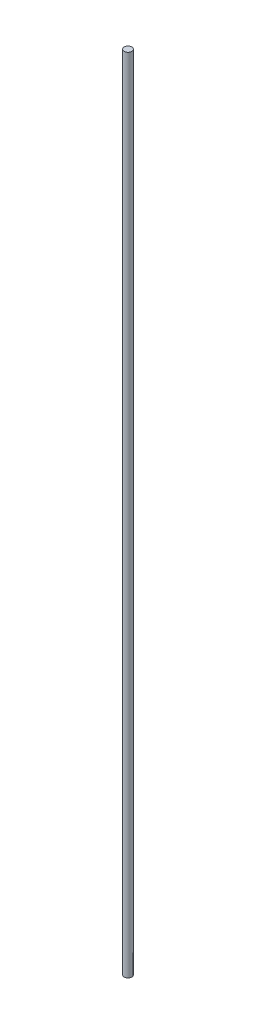
SolidWorks part; units mm, degrees
ref_plane "Front" through (0, 0, 0) normal (0, 0, 1) x (1, 0, 0)
ref_plane "Top" through (0, 0, 0) normal (0, 1, 0) x (1, 0, 0)
ref_plane "Right" through (0, 0, 0) normal (1, 0, 0) x (0, 0, -1)
sketch "Sketch1" plane through (0, 0, 0) normal (0, 1, 0) x (1, 0, 0)
  circle A0 centre (0, 0) radius 3.175
  dimension "D1" = 6.35
extrude "Boss-Extrude1" add sketch "Sketch1" along normal blind 330.2 and the other way blind 330.2
